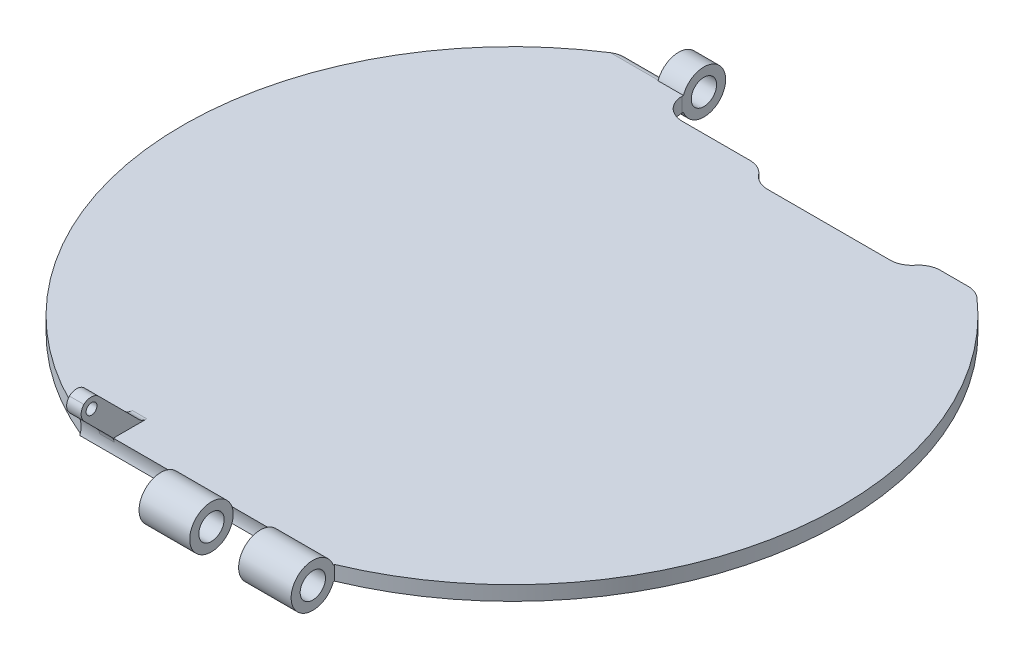
SolidWorks part; units mm, degrees
ref_plane "Front Plane" through (0, 0, 0) normal (0, 0, 1) x (1, 0, 0)
ref_plane "Top Plane" through (0, 0, 0) normal (0, 1, 0) x (1, 0, 0)
ref_plane "Right Plane" through (0, 0, 0) normal (1, 0, 0) x (0, 0, -1)
sketch "Sketch1" plane through (0, 0, 0) normal (0, 1, 0) x (1, 0, 0)
  line L0 (-17.5, -42) -> (17.5, -42)
  line L1 (0, 0) -> (36.3754, 0) construction
  line L2 (-17.5, 42) -> (17.5, 42)
  arc A0 (-17.5, 42) -> (-17.5, -42) centre (0, 0) ccw
  arc A1 (17.5, -42) -> (17.5, 42) centre (0, 0) ccw
  dimension "D1" = 91
  dimension "D2" = 42
  dimension "D3" = 42
extrude "Boss-Extrude1" add sketch "Sketch1" along normal blind 2
sketch "Sketch2" plane through (0, 0, 0) normal (1, 0, 0) x (0, 0, -1)
  line L0 (-43.0566, 1) -> (50.2125, 1) construction
  line L1 (-42, 2) -> (-42, 0) construction
  line L2 (-42, 0) -> (-42.1716, 0)
  line L3 (-42, 0) -> (42, 0) construction
  line L4 (-42, 0) -> (-42, 1)
  line L5 (-42, 1) -> (-42, 2)
  line L6 (-42, 2) -> (-42.1716, 2)
  line L7 (42, 2) -> (-42, 2) construction
  circle A0 centre (-45, 1) radius 1.75
  arc A1 (-42.1716, 2) -> (-42.1716, 0) centre (-45, 1) ccw
  point P4 (-42, 1)
  dimension "D1" = 6
  dimension "D2" = 3.5
extrude "Boss-Extrude2" add sketch "Sketch2" along normal up to vertex (17.5 mm away) and the other way up to vertex (17.5 mm away) up to point (17.5, 2, 42) other way up to point (-17.5, 2, 42)
ref_plane "Plane1" through (3.5, 0, 0) normal (1, 0, 0) x (0, 0, -1)
sketch "Sketch3" plane through (3.5, 0, 0) normal (1, 0, 0) x (0, 0, -1)
  circle A0 centre (-45, 1) radius 3
  arc A1 (-42.1716, 2) -> (-42.1716, 0) centre (-45, 1) ccw construction
extrude "Cut-Extrude1" cut sketch "Sketch3" along normal blind 6.75
mirror "Mirror1" about plane through (0, 0, 0) normal (1, 0, 0) of "Cut-Extrude1"
sketch "Sketch4" plane through (0, 2, 0) normal (0, 1, 0) x (1, 0, 0)
  line L0 (17.5, 42) -> (-17.5, 42) construction
  line L1 (0.75, 42) -> (21.25, 42)
  line L2 (0.75, 35) -> (0.75, 32.75)
  line L3 (0.75, 32.75) -> (21.25, 32.75)
  line L4 (21.25, 42) -> (21.25, 32.75)
  line L6 (0.75, 42) -> (-17.5, 42)
  line L8 (0.75, 35) -> (-17.5, 35)
  line L9 (-17.5, 42) -> (-17.5, 35)
  point P6 (17.5, 42)
  dimension "D1" = 9.25
  dimension "D2" = 16.75
  dimension "D3" = 3.75
  dimension "D4" = 7
  dimension "D5" = 18.25
extrude "Cut-Extrude2" cut sketch "Sketch4" against normal up to surface (2 mm away) up to face at (0, 0, 25.3029)
sketch "Sketch5" plane through (-17.5, 0, 0) normal (1, 0, 0) x (0, 0, -1)
  line L0 (36.24, 1) -> (48.3245, 1) construction
  line L1 (35, 0) -> (42, 0) construction
  line L2 (42, 2) -> (35, 2) construction
  line L3 (41, 2.8351) -> (41, -0.8726) construction
  line L4 (42, 2) -> (42, 0) construction
  line L5 (35, 1) -> (35, 2)
  line L6 (35, 2) -> (38.1716, 2)
  line L7 (35, 1) -> (35, 0)
  line L8 (35, 0) -> (38.1716, 0)
  line L10 (35, 0) -> (35, 2) construction
  arc A0 (38.1716, 0) -> (38.1716, 2) centre (41, 1) ccw
  dimension "D1" = 6
  dimension "D2" = 1
extrude "Boss-Extrude4" add sketch "Sketch5" along normal blind 3 and the other way blind 0.5
sketch "Sketch6" plane through (-14.5, 0, 0) normal (1, 0, 0) x (0, 0, -1)
  circle A0 centre (41, 1) radius 1.75
  arc A1 (38.1716, 0) -> (38.1716, 2) centre (41, 1) ccw construction
  dimension "D1" = 3.5
extrude "Cut-Extrude3" cut sketch "Sketch6" against normal through all
fillet "Fillet1" radius 1 2 edges at (-20.2356, 0, -39.5639) (-20.2356, 2, -39.5639)
sketch "Sketch7" plane through (0, 2, 0) normal (0, 1, 0) x (1, 0, 0)
  line L1 (20.25, 35) -> (29.25, 35)
  line L2 (20.25, 35) -> (20.25, 41)
  line L3 (20.25, 41) -> (29.25, 41)
  line L4 (29.25, 35) -> (29.25, 41)
  line L8 (21.25, 32.75) -> (21.25, 40.2329) construction
  line L9 (-14.5, 35) -> (0.75, 35) construction
  point P8 (20.25, 41)
  point P9 (0, 0)
  point P10 (29.25, 35)
  point P11 (29.25, 41)
  point P12 (20.25, 35)
  point P13 (0, 0)
  dimension "D1" = 9
  dimension "D2" = 6
  dimension "D3" = 1
extrude "Cut-Extrude4" cut sketch "Sketch7" against normal up to surface (2 mm away) up to face at (-2.5773, 0, 0.6941)
fillet "Fillet2" radius 3 4 edges at (29.0732, 1, -35) (21.25, 1, -35) (0.75, 1, -35) (-14.5, 1, -35)
fillet "Fillet3" radius 3 2 edges at (21.25, 1, -32.75) (0.75, 1, -32.75)
ref_plane "Plane3" through (-13.875, 0, 0) normal (-1, 0, 0) x (0, 0, 1)
sketch "Sketch10" plane through (-13.875, 0, 0) normal (-1, 0, 0) x (0, 0, 1)
  circle A1 centre (45, 1) radius 3
  arc A2 (42.1716, 0) -> (42.1716, 2) centre (45, 1) ccw construction
extrude "Cut-Extrude5" cut sketch "Sketch10" against normal up to surface and the other way up to surface up to face at (-10.25, 1, 46.75) other way up to face at (-17.5, 1, 43.25)
sketch "Sketch11" plane through (-13.875, 0, 0) normal (-1, 0, 0) x (0, 0, 1)
  line L0 (38.1716, 2) -> (45.2426, 9.0711)
  line L1 (42, 2) -> (-38.25, 2) construction
  line L2 (45.2426, 9.0711) -> (47.2426, 7.0711)
  line L3 (47.2426, 7.0711) -> (42.1716, 2)
  line L4 (42.1716, 2) -> (38.1716, 2)
  line L5 (46.2426, 8.0711) -> (43.3732, 5.2017) construction
  circle A0 centre (45.182, 7.0104) radius 0.75
  point P8 (0, 0)
  point P11 (0, 0)
  point P13 (0, 0)
  point P14 (0, 0)
  point P15 (41.9463, 2)
  point P16 (0, 0)
  dimension "D3" = 1.5
  dimension "D1" = 45
  dimension "D2" = 10
  dimension "D4" = 4
  dimension "D5" = 1.5
extrude "Boss-Extrude6" add sketch "Sketch11" along normal blind 1 and the other way blind 1
fillet "Fillet5" radius 1.5 4 edges at (-13.875, 2, 42.1716) (-13.875, 7.0711, 47.2426) (-13.875, 9.0711, 45.2426) (-13.875, 2, 38.1716)
